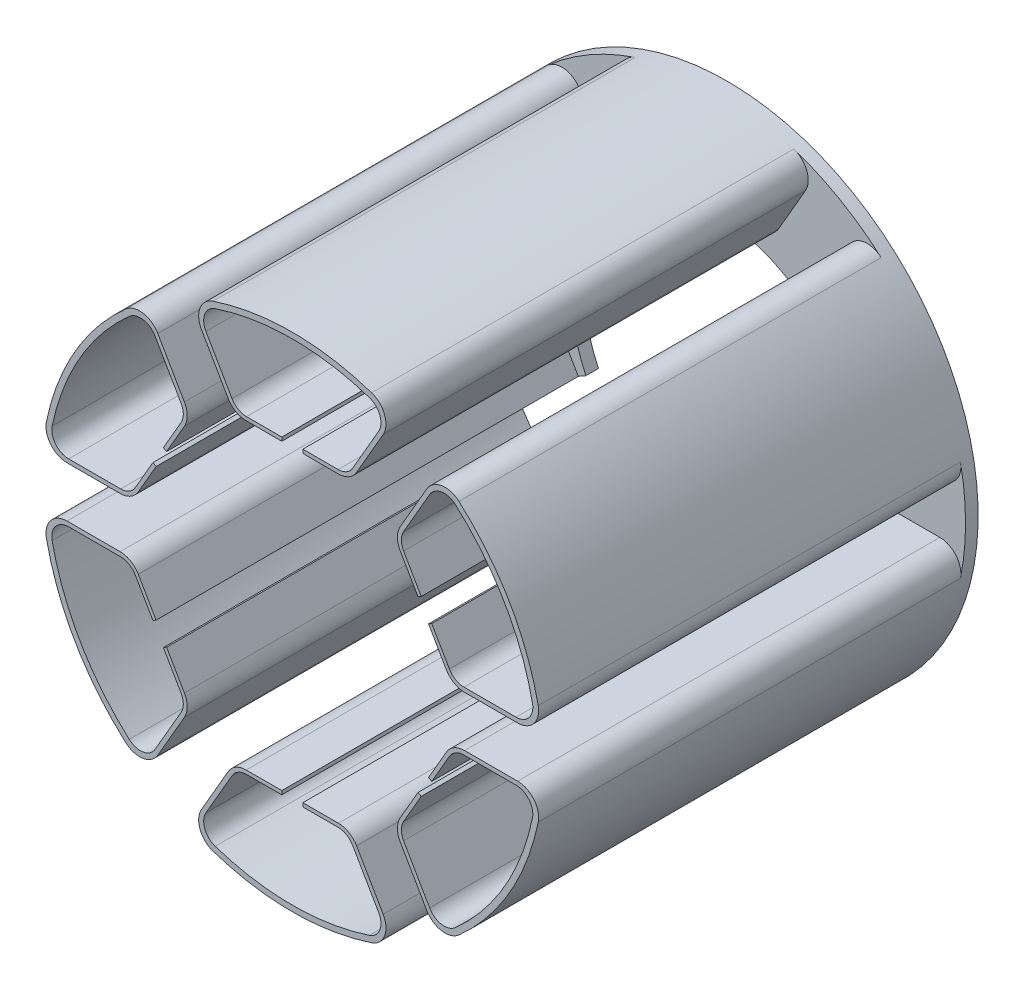
SolidWorks part; units mm, degrees
ref_plane "Ön Düzlem" through (0, 0, 0) normal (0, 0, 1) x (1, 0, 0)
ref_plane "Üst Düzlem" through (0, 0, 0) normal (0, 1, 0) x (1, 0, 0)
ref_plane "Sağ Düzlem" through (0, 0, 0) normal (1, 0, 0) x (0, 0, -1)
sketch "Çizim1" plane through (0, 0, 0) normal (0, 0, 1) x (1, 0, 0)
  line L0 (-5.5426, 14.4) -> (5.5426, 14.4)
  line L1 (9.6995, 12) -> (15.242, 2.4)
  line L2 (15.242, -2.4) -> (9.6995, -12)
  line L3 (5.5426, -14.4) -> (-5.5426, -14.4)
  line L4 (-9.6995, -12) -> (-15.242, -2.4)
  line L5 (-15.242, 2.4) -> (-9.6995, 12)
  line L7 (15.242, 2.4) -> (23.7792, 2.4)
  line L9 (9.6995, 12) -> (13.9681, 19.3934)
  line L10 (9.6995, -12) -> (13.9681, -19.3934)
  line L12 (-5.5426, 14.4) -> (-9.8111, 21.7934)
  line L13 (5.5426, 14.4) -> (9.8111, 21.7934)
  line L14 (15.242, -2.4) -> (23.7792, -2.4)
  line L15 (-5.5426, -14.4) -> (-9.8111, -21.7934)
  line L17 (5.5426, -14.4) -> (9.8111, -21.7934)
  line L18 (-15.242, -2.4) -> (-23.7792, -2.4)
  line L20 (-9.6995, -12) -> (-13.9681, -19.3934)
  line L21 (-9.6995, 12) -> (-13.9681, 19.3934)
  line L23 (-15.242, 2.4) -> (-23.7792, 2.4)
  arc A0 (-23.7792, -2.4) -> (-13.9681, -19.3934) centre (0, 0) ccw
  arc A1 (-13.9681, 19.3934) -> (-23.7792, 2.4) centre (0, 0) ccw
  arc A2 (9.8111, 21.7934) -> (-9.8111, 21.7934) centre (0, 0) ccw
  arc A3 (23.7792, 2.4) -> (13.9681, 19.3934) centre (0, 0) ccw
  arc A4 (13.9681, -19.3934) -> (23.7792, -2.4) centre (0, 0) ccw
  arc A5 (-9.8111, -21.7934) -> (9.8111, -21.7934) centre (0, 0) ccw
  point P1 (0, 0)
  point P6 (0, 14.4)
  point P7 (-7.8785, 22.4052)
  point P18 (0, 0)
  point P21 (23.6284, 2.4)
  point P22 (0, 21.6628)
  point P23 (0, 0)
  point P32 (0, 0)
  point P43 (0, 0)
  dimension "D1" = 47.8
  dimension "D2" = 6
  dimension "D3" = 4.8
  dimension "D4" = 28.8
  dimension "D5" = 120
  dimension "D7" = 120
  dimension "D6" = 6
extrude "Yükseklik-Ekstrüzyon1" add sketch "Çizim1" along normal blind 40.2
sketch "Çizim2" plane through (0, 0, 0) normal (0, 0, -1) x (-1, 0, 0)
  circle A0 centre (0, 0) radius 23.9
  circle A1 centre (0, 0) radius 13.6
  dimension "D1" = 47.8
  dimension "D2" = 27.2
extrude "Yükseklik-Ekstrüzyon2" add sketch "Çizim2" along normal blind 1.2
fillet "Radyus1" radius 2 24 edges at (13.9681, 19.3934, 20.1) (-13.9681, 19.3934, 20.1) (-23.7792, -2.4, 20.1) (-15.242, -2.4, 20.1) (-5.5426, -14.4, 20.1) (5.5426, -14.4, 20.1) (15.242, -2.4, 20.1) (9.6995, -12, 20.1) (23.7792, 2.4, 20.1) (23.7792, -2.4, 20.1) (13.9681, -19.3934, 20.1) (-9.8111, -21.7934, 20.1) (9.8111, -21.7934, 20.1) (-13.9681, -19.3934, 20.1) (-9.6995, -12, 20.1) (-9.6995, 12, 20.1) (-15.242, 2.4, 20.1) (-23.7792, 2.4, 20.1) (15.242, 2.4, 20.1) (9.8111, 21.7934, 20.1) (5.5426, 14.4, 20.1) (9.6995, 12, 20.1) (-5.5426, 14.4, 20.1) (-9.8111, 21.7934, 20.1)
sketch "Çizim3" plane through (0, 0, 40.2) normal (0, 0, 1) x (1, 0, 0)
  line L36 (-10.5944, 12.75) -> (-13.075, 17.0466)
  line L37 (-21.3003, 2.8) -> (-16.339, 2.8)
  line L38 (-14.9534, 3.6) -> (-10.5944, 11.15)
  line L39 (4.359, -14.75) -> (-4.359, -14.75)
  line L40 (-5.7446, -15.55) -> (-8.2253, -19.8466)
  line L41 (8.2253, -19.8466) -> (5.7446, -15.55)
  line L42 (-16.339, -2.8) -> (-21.3003, -2.8)
  line L43 (-13.075, -17.0466) -> (-10.5944, -12.75)
  line L44 (-10.5944, -11.15) -> (-14.9534, -3.6)
  line L45 (21.3003, -2.8) -> (16.339, -2.8)
  line L46 (14.9534, -3.6) -> (10.5944, -11.15)
  line L47 (10.5944, -12.75) -> (13.075, -17.0466)
  line L48 (13.075, 17.0466) -> (10.5944, 12.75)
  line L49 (10.5944, 11.15) -> (14.9534, 3.6)
  line L50 (16.339, 2.8) -> (21.3003, 2.8)
  line L51 (5.7446, 15.55) -> (8.2253, 19.8466)
  line L52 (-8.2253, 19.8466) -> (-5.7446, 15.55)
  line L53 (-4.359, 14.75) -> (4.359, 14.75)
  arc A60 (-13.075, 17.0466) -> (-15.5244, 17.4417) centre (-14.4607, 16.2466) ccw
  arc A61 (-15.5244, 17.4417) -> (-22.8672, 4.7237) centre (0, 0) ccw
  arc A62 (-22.8672, 4.7237) -> (-21.3003, 2.8) centre (-21.3003, 4.4) ccw
  arc A63 (-16.339, 2.8) -> (-14.9534, 3.6) centre (-16.339, 4.4) ccw
  arc A64 (-10.5944, 11.15) -> (-10.5944, 12.75) centre (-11.98, 11.95) ccw
  arc A65 (-4.359, -14.75) -> (-5.7446, -15.55) centre (-4.359, -16.35) ccw
  arc A66 (-8.2253, -19.8466) -> (-7.3428, -22.1654) centre (-6.8396, -20.6466) ccw
  arc A67 (-7.3428, -22.1654) -> (7.3428, -22.1654) centre (0, 0) ccw
  arc A68 (7.3428, -22.1654) -> (8.2253, -19.8466) centre (6.8396, -20.6466) ccw
  arc A69 (5.7446, -15.55) -> (4.359, -14.75) centre (4.359, -16.35) ccw
  arc A70 (-21.3003, -2.8) -> (-22.8672, -4.7237) centre (-21.3003, -4.4) ccw
  arc A71 (-22.8672, -4.7237) -> (-15.5244, -17.4417) centre (0, 0) ccw
  arc A72 (-15.5244, -17.4417) -> (-13.075, -17.0466) centre (-14.4607, -16.2466) ccw
  arc A73 (-10.5944, -12.75) -> (-10.5944, -11.15) centre (-11.98, -11.95) ccw
  arc A74 (-14.9534, -3.6) -> (-16.339, -2.8) centre (-16.339, -4.4) ccw
  arc A75 (16.339, -2.8) -> (14.9534, -3.6) centre (16.339, -4.4) ccw
  arc A76 (10.5944, -11.15) -> (10.5944, -12.75) centre (11.98, -11.95) ccw
  arc A77 (13.075, -17.0466) -> (15.5244, -17.4417) centre (14.4607, -16.2466) ccw
  arc A78 (15.5244, -17.4417) -> (22.8672, -4.7237) centre (0, 0) ccw
  arc A79 (22.8672, -4.7237) -> (21.3003, -2.8) centre (21.3003, -4.4) ccw
  arc A80 (22.8672, 4.7237) -> (15.5244, 17.4417) centre (0, 0) ccw
  arc A81 (15.5244, 17.4417) -> (13.075, 17.0466) centre (14.4607, 16.2466) ccw
  arc A82 (10.5944, 12.75) -> (10.5944, 11.15) centre (11.98, 11.95) ccw
  arc A83 (14.9534, 3.6) -> (16.339, 2.8) centre (16.339, 4.4) ccw
  arc A84 (21.3003, 2.8) -> (22.8672, 4.7237) centre (21.3003, 4.4) ccw
  arc A85 (8.2253, 19.8466) -> (7.3428, 22.1654) centre (6.8396, 20.6466) ccw
  arc A86 (7.3428, 22.1654) -> (-7.3428, 22.1654) centre (0, 0) ccw
  arc A87 (-7.3428, 22.1654) -> (-8.2253, 19.8466) centre (-6.8396, 20.6466) ccw
  arc A88 (-5.7446, 15.55) -> (-4.359, 14.75) centre (-4.359, 16.35) ccw
  arc A89 (4.359, 14.75) -> (5.7446, 15.55) centre (4.359, 16.35) ccw
extrude "Kes-Ekstrüzyon1" cut sketch "Çizim3" against normal up to surface (41.4 mm away) up to face at (-23.9, 0, -1.2)
sketch "Çizim4" plane through (0, 0, 40.2) normal (0, 0, 1) x (1, 0, 0)
  line L0 (-4.359, 14.75) -> (4.359, 14.75) construction
  line L1 (-1, 12.25) -> (1, 12.25)
  line L2 (-1, 12.25) -> (-1, 14.75)
  line L3 (-1, 14.75) -> (1, 14.75)
  line L4 (1, 12.25) -> (1, 14.75)
  line L5 (-1, 12.25) -> (1, 14.75) construction
  line L6 (-1, 14.75) -> (1, 12.25) construction
  line L7 (10.1088, 6.991) -> (12.2739, 8.241)
  line L8 (10.1088, 6.991) -> (11.1088, 5.259)
  line L9 (11.1088, 5.259) -> (13.2739, 6.509)
  line L10 (12.2739, 8.241) -> (13.2739, 6.509)
  line L11 (11.1088, -5.259) -> (13.2739, -6.509)
  line L12 (11.1088, -5.259) -> (10.1088, -6.991)
  line L13 (10.1088, -6.991) -> (12.2739, -8.241)
  line L14 (13.2739, -6.509) -> (12.2739, -8.241)
  line L15 (1, -12.25) -> (1, -14.75)
  line L16 (1, -12.25) -> (-1, -12.25)
  line L17 (-1, -12.25) -> (-1, -14.75)
  line L18 (1, -14.75) -> (-1, -14.75)
  line L19 (-10.1088, -6.991) -> (-12.2739, -8.241)
  line L20 (-10.1088, -6.991) -> (-11.1088, -5.259)
  line L21 (-11.1088, -5.259) -> (-13.2739, -6.509)
  line L22 (-12.2739, -8.241) -> (-13.2739, -6.509)
  line L23 (-11.1088, 5.259) -> (-13.2739, 6.509)
  line L24 (-11.1088, 5.259) -> (-10.1088, 6.991)
  line L25 (-10.1088, 6.991) -> (-12.2739, 8.241)
  line L26 (-13.2739, 6.509) -> (-12.2739, 8.241)
  point P0 (0, 13.5)
  point P10 (0, 0)
  point P30 (0, 0)
  dimension "D1" = 2
  dimension "D2" = 2.5
  dimension "D3" = 6
extrude "Kes-Ekstrüzyon2" cut sketch "Çizim4" against normal up to surface (41.4 mm away) up to face at (0, -18.2321, -1.2)
